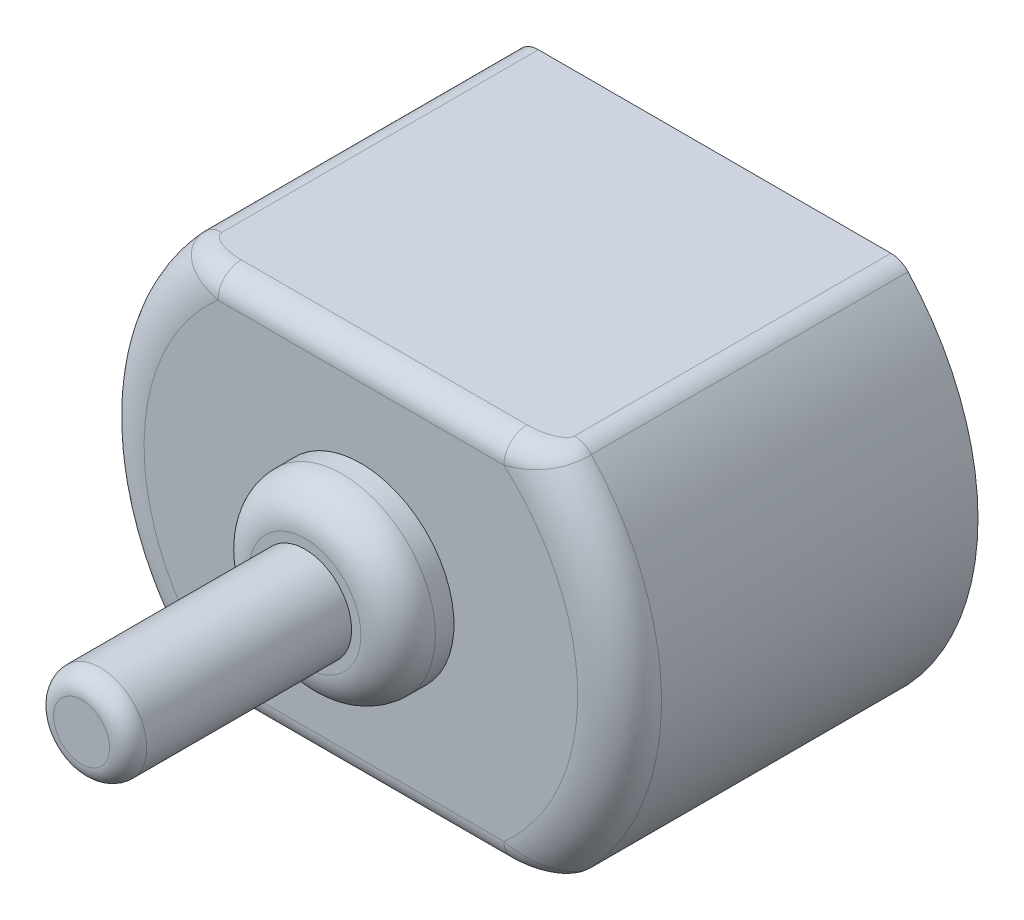
SolidWorks part; units mm, degrees
ref_plane "Front Plane" through (0, 0, 0) normal (0, 0, 1) x (1, 0, 0)
ref_plane "Top Plane" through (0, 0, 0) normal (0, 1, 0) x (1, 0, 0)
ref_plane "Right Plane" through (0, 0, 0) normal (1, 0, 0) x (0, 0, -1)
sketch "Sketch1" plane through (0, 0, 0) normal (0, 0, 1) x (1, 0, 0)
  line L1 (-10, 10) -> (10, 10)
  line L2 (-10, 10) -> (-10, -10) construction
  line L3 (-10, -10) -> (10, -10)
  line L4 (10, 10) -> (10, -10) construction
  line L5 (-10, 10) -> (10, -10) construction
  line L6 (-10, -10) -> (10, 10) construction
  circle A0 centre (0, 0) radius 14.1421 construction
  arc A1 (10, 10) -> (10, -10) centre (0, 0) cw
  arc A2 (-10, 10) -> (-10, -10) centre (0, 0) ccw
  point P0 (0, 0)
  dimension "D1" = 20
  dimension "D2" = 20
extrude "Boss-Extrude1" add sketch "Sketch1" along normal mid plane 19
fillet "Fillet1" radius 2 2 edges at (-14.1421, 0, 9.5) (14.1421, 0, 9.5) second distance 2.5 first distance on face at (-12.0711, 0, 0) first distance on face at (12.0711, 0, 0)
fillet "Fillet2" radius 1.25 10 edges
sketch "Sketch2" plane through (0, 0, 9.5) normal (0, 0, 1) x (1, 0, 0)
  line L2 (-7.6798, -8.75) -> (7.6798, -8.75)
  line L3 (7.6798, 8.75) -> (-7.6798, 8.75)
  line L4 (-7.6798, -8.75) -> (7.6798, -8.75)
  line L5 (7.6798, 8.75) -> (-7.6798, 8.75)
  circle A0 centre (0, 0) radius 5
  spline S2 degree 2 poles (2719.0295, -2912.137) (99.0463, 117.809) (-8.3178, 8.1455) (-9.3768, 7.0638) (-10.1226, 5.7505) (-10.87, 4.4344) (-11.2558, 2.9739) (-11.642, 1.5118) (-11.642, 0) (-11.6421, -1.5106) (-11.2558, -2.9739) (-10.8704, -4.4334) (-10.1226, -5.7505) (-9.3774, -7.0629) (-8.3178, -8.1454) (98.967, -117.7481) (2727.1916, 2904.5998) knots -12.57593 -12.57593 -12.57593 0.125 0.125 0.25 0.25 0.375 0.375 0.5 0.5 0.625 0.625 0.75 0.75 0.875 0.875 13.572234 13.572234 13.572234 only from (-7.6798, 8.75) to (-7.6798, -8.75)
  spline S3 degree 2 poles (-2719.0295, 2912.137) (-99.0463, -117.809) (8.3178, -8.1455) (9.3768, -7.0638) (10.1226, -5.7505) (10.87, -4.4344) (11.2558, -2.9739) (11.642, -1.5118) (11.642, 0) (11.6421, 1.5106) (11.2558, 2.9739) (10.8704, 4.4334) (10.1226, 5.7505) (9.3774, 7.0629) (8.3178, 8.1454) (-98.967, 117.7481) (-2727.1916, -2904.5998) knots -12.57593 -12.57593 -12.57593 0.125 0.125 0.25 0.25 0.375 0.375 0.5 0.5 0.625 0.625 0.75 0.75 0.875 0.875 13.572234 13.572234 13.572234 only from (7.6798, -8.75) to (7.6798, 8.75)
  spline S4 degree 2 poles (-7.6798, 8.75) (-8.0092, 8.4607) (-8.3178, 8.1455) (-9.3768, 7.0638) (-10.1226, 5.7505) (-10.87, 4.4344) (-11.2558, 2.9739) (-11.642, 1.5118) (-11.642, 0) (-11.6421, -1.5106) (-11.2558, -2.9739) (-10.8704, -4.4334) (-10.1226, -5.7505) (-9.3774, -7.0629) (-8.3178, -8.1454) (-8.0092, -8.4607) (-7.6798, -8.75) knots 0.088489 0.088489 0.088489 0.125 0.125 0.25 0.25 0.375 0.375 0.5 0.5 0.625 0.625 0.75 0.75 0.875 0.875 0.911519 0.911519 0.911519
  spline S5 degree 2 poles (7.6798, -8.75) (8.0092, -8.4607) (8.3178, -8.1455) (9.3768, -7.0638) (10.1226, -5.7505) (10.87, -4.4344) (11.2558, -2.9739) (11.642, -1.5118) (11.642, 0) (11.6421, 1.5106) (11.2558, 2.9739) (10.8704, 4.4334) (10.1226, 5.7505) (9.3774, 7.0629) (8.3178, 8.1454) (8.0092, 8.4607) (7.6798, 8.75) knots 0.088489 0.088489 0.088489 0.125 0.125 0.25 0.25 0.375 0.375 0.5 0.5 0.625 0.625 0.75 0.75 0.875 0.875 0.911519 0.911519 0.911519
  dimension "D1" = 0
extrude "Boss-Extrude3" add sketch "Sketch2" along normal blind 3 contours A0
fillet "Fillet4" radius 2 1 edges at (5, 0, 12.5)
sketch "Sketch3" plane through (0, 0, 12.5) normal (0, 0, 1) x (1, 0, 0)
  circle A0 centre (0, 0) radius 2.5
extrude "Boss-Extrude4" add sketch "Sketch3" along normal blind 12
fillet "Fillet5" radius 1 1 edges at (2.5, 0, 24.5)
sketch "Sketch4" plane through (0, -10, 0) normal (0, -1, 0) x (1, 0, 0)
  circle A0 centre (-5, 0) radius 2
  circle A1 centre (5, 0) radius 2
  point P0 (-5, 0)
  point P1 (5, 0)
  point P2 (-5, 0)
extrude "Cut-Extrude2" cut sketch "Sketch4" against normal blind 2
